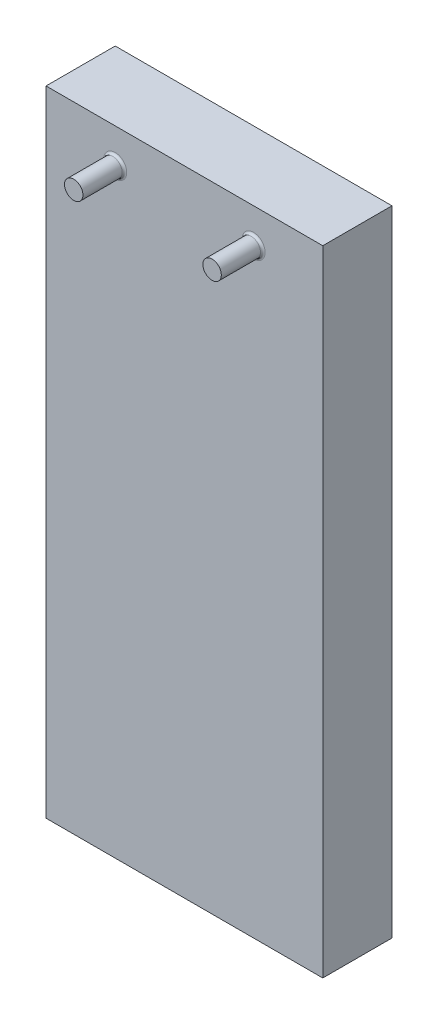
SolidWorks part; units mm, degrees
ref_plane "Front Plane" through (0, 0, 0) normal (0, 0, 1) x (1, 0, 0)
ref_plane "Top Plane" through (0, 0, 0) normal (0, 1, 0) x (1, 0, 0)
ref_plane "Right Plane" through (0, 0, 0) normal (1, 0, 0) x (0, 0, -1)
sketch "Sketch1" plane through (0, 0, 0) normal (0, 1, 0) x (1, 0, 0)
  line L1 (-60, -15) -> (60, -15)
  line L2 (-60, -15) -> (-60, 15)
  line L3 (-60, 15) -> (60, 15)
  line L4 (60, -15) -> (60, 15)
  line L5 (-60, -15) -> (60, 15) construction
  line L6 (-60, 15) -> (60, -15) construction
  point P0 (0, 0)
  dimension "D1" = 120
  dimension "D2" = 30
extrude "Boss-Extrude1" add sketch "Sketch1" along normal blind 275
sketch "Sketch2" plane through (0, 0, 15) normal (0, 0, 1) x (1, 0, 0)
  line L0 (-60, 245) -> (60, 245)
  line L1 (-60, 275) -> (-60, 0) construction
  line L2 (60, 275) -> (60, 0) construction
  line L3 (-60, 275) -> (60, 275) construction
  line L4 (-60, 245) -> (-60, 275)
  line L5 (-60, 260) -> (60, 260) construction
  circle A2 centre (-30, 260) radius 4
  circle A3 centre (30, 260) radius 4
  dimension "D4" = 8
  dimension "D1" = 30
  dimension "D2" = 30
  dimension "D3" = 30
extrude "Boss-Extrude2" add sketch "Sketch2" along normal blind 18 contours L5 A3 | A3 L5 | L5 A2 | A2 L5 region at (-30, 261.6977, 15) region at (30, 261.6977, 15) region at (30, 258.3023, 15) region at (-30, 258.3023, 15)
fillet "Fillet1" radius 1 2 edges at (26, 260, 15) (-34, 260, 15)
equation "\"PCWidth\"= 172mm"
equation "\"PCLength\"= 320mm"
equation "\"PCHeight\"= 242mm"
equation "\"WallThickness\"= 10mm"
equation "\"ThermoBarrierThickness\"= 3mm"
equation "\"HotSideGap\"= 50mm"
equation "\"PCClearance\"= 25mm"
equation "\"RadiatorHeight\"= 275mm"
equation "\"D1@Boss-Extrude1\"=\"RadiatorHeight\""
